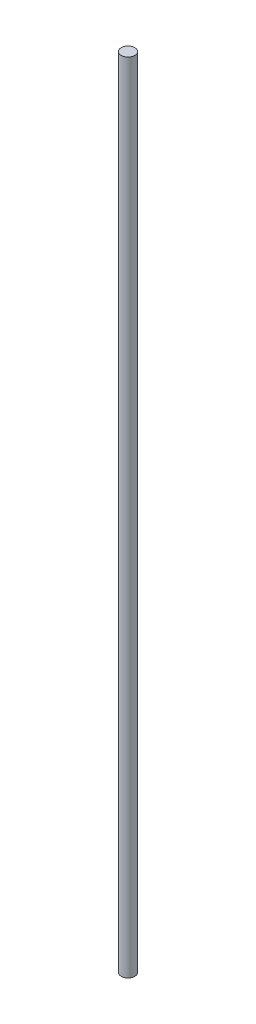
SolidWorks part; units mm, degrees
ref_plane "Спереди" through (0, 0, 0) normal (0, 0, 1) x (1, 0, 0)
ref_plane "Сверху" through (0, 0, 0) normal (0, 1, 0) x (1, 0, 0)
ref_plane "Справа" through (0, 0, 0) normal (1, 0, 0) x (0, 0, -1)
sketch "Эскиз2" plane through (0, 0, 0) normal (0, 0, 1) x (1, 0, 0)
  line L5 (-2.5, 147) -> (0, 147)
  line L6 (-2.5, 147) -> (-2.5, -147)
  line L7 (-2.5, -147) -> (0, -147)
  line L8 (0, 147) -> (0, -147)
  line L9 (-2.5, 147) -> (0, -147) construction
  line L10 (-2.5, -147) -> (0, 147) construction
  point P0 (-1.25, 0)
  point P5 (0, 0)
  dimension "D1" = 2.5
  dimension "D2" = 294
revolve "Повернуть1" add sketch "Эскиз2" angle 360 about L6
equation "\"Ширина груза\"= 160"
equation "\"Глубина груза\"= 240"
equation "\"Высота груза\"= 160"
equation "\"Ширина ячейки\"= \"Ширина груза\" + 10"
equation "\"Глубина ячейки\"= \"Глубина груза\" + 10"
equation "\"Высота ячейки\"= \"Высота груза\" + 10 + 13"
equation "\"Колво ячеек ширина\"= 2"
equation "\"Колво ячеек высота\"= 2"
equation "\"Толщина стенки\"= \"Толщина тонких панелей\""
equation "\"Крепление дверцы\"= 5 "
equation "\"Ширина рейки\"= \"Толщина шестерни\""
equation "\"Высота рейки\"= 20"
equation "\"Высота пола\"= 2*\"Толщина тонких панелей\""
equation "\"Колво полозьев\"= 5"
equation "\"Отступ рейки\"= 20"
equation "\"Глубина каретки\"= \"Глубина ячейки\" + 30 + \"Мотор Y высота корпуса\" + 20"
equation "\"Длинна рейки\"= (\"Ширина ячейки\"+\"Толщина вертикальных стенок\"+\"Крепление дверцы\")*\"Колво ячеек ширина\"+\"Ширина ячейки выгрузки\"*\"Колво выгрузки\"+\"Толщина вертикальных стенок\"+2*\"Отступ крепления мотора фиксации\"-\"Крепление дверцы\"*\"Колво ячеек ширина\""
equation "\"Отступ шпильки\"= 26"
equation "\"Диаметр шпильки\"= 5"
equation "\"Длинна шпильки\"= (\"Высота ячейки\"+\"Толщина горизонтальных плит\"+\"Высота пола\")*\"Колво ячеек высота\"+2*(\"Толщина горизонтальных плит\"+\"Отступ рейки\")"
equation "\"D1@Эскиз2\"= \"Диаметр шпильки\" / 2"
equation "\"D2@Эскиз2\" = \"Глубина каретки\" - \"Мотор Y высота корпуса\" - \"Толщина стенки\""
equation "\"Ширина пластины\"= 50  "
equation "\"Высота зона выгрузки\"= \"Высота ячейки\" * 2 + \"Толщина стенки\" * 2"
equation "\"Колво выгрузки\"= 1"
equation "\"Отступ крепления мотора фиксации\"= (\"Ширина пластины\"+20-\"Толщина вертикальных стенок\")/2"
equation "\"Мотор X ширина корпуса\"= 42.3"
equation "\"Мотор X высота корпуса\"= 42.3"
equation "\"Мотор X длина корпуса\"= 40"
equation "\"Мотор X вылет вала\"= 19.8"
equation "\"Мотор Y ширина корпуса\"= 42.3"
equation "\"Мотор Y высота корпуса\"= 42.3"
equation "\"Мотор Y длина корпуса\"= 48"
equation "\"Мотор Y вылет вала\"= 30"
equation "\"Мотор Z ширина корпуса\"= 42"
equation "\"Мотор Z высота корпуса\"= 42"
equation "\"Мотор Z длина корпуса\"= 40"
equation "\"Мотор Z вылет вала\"= 23"
equation "\"Мотор диаметр вала ПРЕДВ\"= 5"
equation "\"Мотор шаг крепления ПРЕДВ\"= 31"
equation "\"Мотор диаметр отверстий ПРЕДВ\"= 3"
equation "\"Мотор глубина отверстий ПРЕДВ\"= 4.5"
equation "\"Мотор диаметр буртика ПРЕДВ\"= 22"
equation "\"Мотор высота буртика ПРЕДВ\"= 2"
equation "\"Мотор диаметр шкива ПРЕДВ\"= 16"
equation "\"Мотор длина шкива ПРЕДВ\"= 12"
equation "\"Мотор отступ шкива ПРЕДВ\"= 5"
equation "\"Мотор X шаг градусов\"= 1.8"
equation "\"Мотор X ток А\"= 1.5"
equation "\"Мотор X сопротивление Ом\"= 1.3"
equation "\"Мотор X индуктивность мГн\"= 2"
equation "\"Мотор Y шаг градусов\"= 1.8"
equation "\"Мотор Y ток А\"= 2.2"
equation "\"Мотор Y сопротивление Ом\"= 0.9"
equation "\"Мотор Y индуктивность мГн\"= 2"
equation "\"Мотор Z шаг градусов\"= 1.8"
equation "\"Мотор Z ток А\"= 1"
equation "\"Мотор Z сопротивление Ом\"= 4"
equation "\"Мотор Z индуктивность мГн\"= 8"
equation "\"Мотор Y диаметр ротора\"= 25.78"
equation "\"Ширина ячейки выгрузки\"= \"Ширина ячейки\"+\"Толщина вертикальных стенок\"+2*\"Отступ крепления мотора фиксации\""
equation "\"Толщина тонких панелей\"= 6"
equation "\"Толщина вертикальных стенок\"= 6"
equation "\"Толщина горизонтальных плит\"= 6"
equation "\"Базовая высота корпуса\"= (\"Высота ячейки\"+\"Толщина тонких панелей\"+\"Высота пола\")*\"Колво ячеек высота\"+6*\"Толщина тонких панелей\"+\"Мотор X ширина корпуса\"+\"Мотор Y ширина корпуса\"+75"
equation "\"Высота корпуса\"= (\"Высота ячейки\"+\"Толщина горизонтальных плит\"+\"Высота пола\")*\"Колво ячеек высота\"+2*\"Толщина горизонтальных плит\"+4*\"Толщина тонких панелей\"+\"Мотор X ширина корпуса\"+\"Мотор Y ширина корпуса\"+75"
equation "\"Смещение центра корпуса\"= (\"Высота корпуса\"-\"Базовая высота корпуса\")/2-(\"Толщина горизонтальных плит\"-\"Толщина тонких панелей\")"
equation "\"Отметка пола\"= -\"Базовая высота корпуса\"/2+\"Толщина тонких панелей\""
equation "\"Отметка потолка\"= \"Отметка пола\"+\"Высота корпуса\"-2*\"Толщина горизонтальных плит\""
equation "\"Отметка верхней полки\"= \"Отметка потолка\"-(28+\"Толщина тонких панелей\")-\"Высота ячейки\"-\"Высота пола\""
equation "\"Отметка нижней полки\"= \"Отметка верхней полки\"-\"Высота ячейки\"-\"Высота пола\"-\"Толщина горизонтальных плит\""
equation "\"Толщина шестерни\"= 10"
